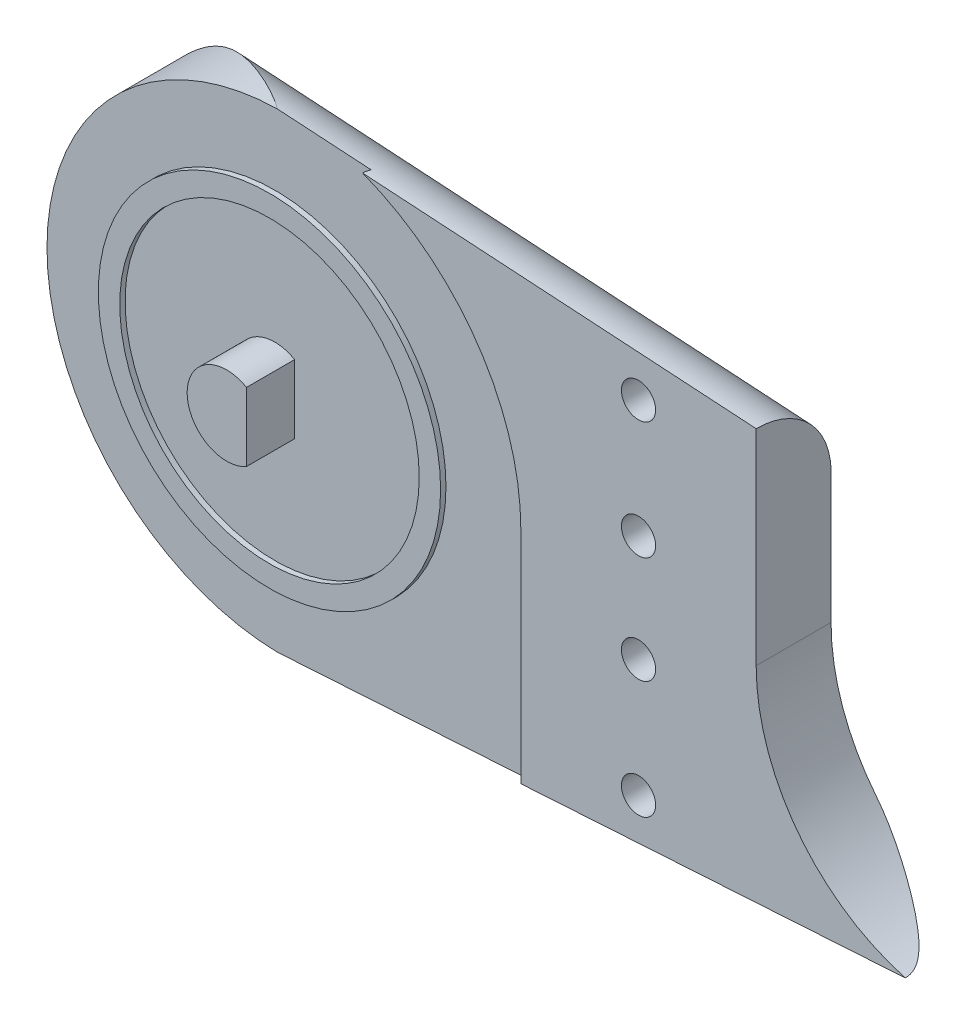
SolidWorks part; units mm, degrees
ref_plane "Front" through (0, 0, 0) normal (0, 0, 1) x (1, 0, 0)
ref_plane "Top" through (0, 0, 0) normal (0, 1, 0) x (1, 0, 0)
ref_plane "Right" through (0, 0, 0) normal (1, 0, 0) x (0, 0, -1)
sketch "Sketch1" plane through (0, 0, 0) normal (0, 0, 1) x (1, 0, 0)
  line L0 (0, 0) -> (-32, 0) construction
  line L2 (-32, 11) -> (-2.5264, 9.1579)
  line L3 (-32, -11) -> (-2.5264, -9.1579)
  line L4 (-9.5, 0) -> (-9.5, 9.5938)
  circle A0 centre (0, 0) radius 9.5
  circle A1 centre (-32, 0) radius 11
  circle A2 centre (0, 0) radius 9
extrude "Boss-Extrude1" add sketch "Sketch1" along normal blind 3.5 contours L2 A1 L3 | A1 L3 A0 L2 | L0 A1 L3 region at (-16.0478, -0.4531, 0) region at (-32.0001, 0, 0)
sketch "Sketch7" plane through (0, 0, 0) normal (0, 0, 1) x (1, 0, 0)
  line L0 (-20.5, 0) -> (-20.5, -11.5)
  line L1 (-20.5, -11.5) -> (-32, -11.5)
  circle A0 centre (-32, 0) radius 11.5
extrude "Joint Hole" cut sketch "Sketch7" against normal blind 0.35 from offset 3.5 contours A0 | A0 L1 L0 region at (-32, 0, 0) region at (-23.0687, -8.9313, 0)
sketch "Sketch5" plane through (0, 0, 0) normal (0, 0, 1) x (1, 0, 0)
  line L0 (-32, 0) -> (-31.075, 0) construction
  line L1 (-31.075, -1.6021) -> (-31.075, 1.6021)
  arc A1 (-31.075, -1.6021) -> (-31.075, 1.6021) centre (-32, 0) cw
extrude "Pot Insert" add sketch "Sketch5" along normal blind 2.25 from offset 3.5
sketch "Sketch4" plane through (0, 0, 0) normal (0, 0, 1) x (1, 0, 0)
  circle A0 centre (-32, 0) radius 8
  circle A1 centre (-32, 0) radius 7
extrude "Friction" add sketch "Sketch4" along normal blind 0.25 from offset 3.5
sketch "Sketch2" plane through (0, 0, 0) normal (0, 0, 1) x (1, 0, 0)
  line L0 (0, 0) -> (-15, 0) construction
  line L1 (-15, 0) -> (-15, 2.5) construction
  line L2 (-15, 0) -> (-15, -8) construction
  line L3 (-15, 0) -> (-15, 8) construction
  line L4 (-15, 0) -> (-15, -2.5) construction
  circle A0 centre (-15, 8) radius 0.8
  circle A1 centre (-15, -8) radius 0.8
  circle A2 centre (-15, 2.5) radius 0.8
  circle A3 centre (-15, -2.5) radius 0.8
extrude "Screw Holes" cut sketch "Sketch2" along normal through all
sketch "Sketch8" plane through (0, 0, 0) normal (0, 0, 1) x (1, 0, 0)
  circle A0 centre (-15, 2.5) radius 1.25
  circle A1 centre (-15, -2.5) radius 1.25
extrude "Screw Heads" cut sketch "Sketch8" along normal blind 2
fillet "Fillet1" radius 3.5 2 edges at (-17.2632, -10.079, 0) (-20.75, 10.2969, 0)
